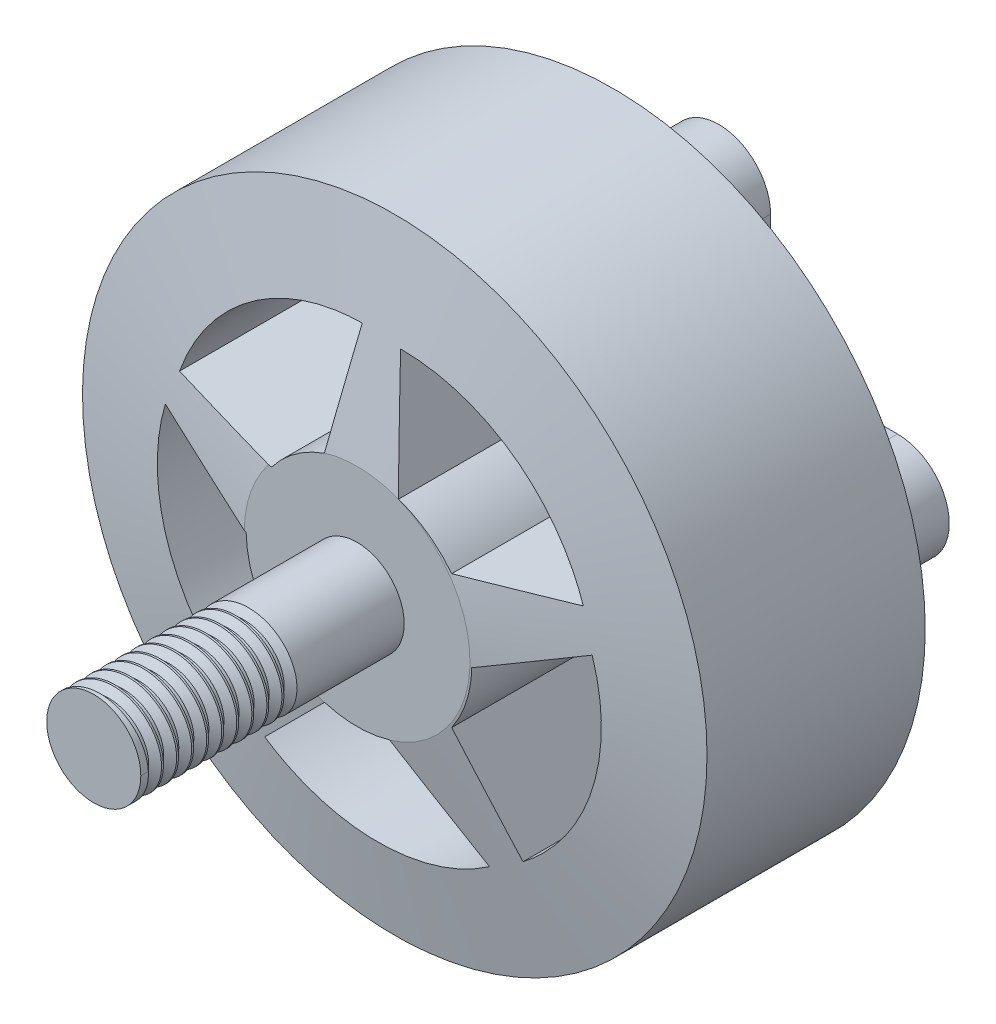
SolidWorks part; units mm, degrees
material "7050-T7651"
ref_plane "Alzado" through (0, 0, 0) normal (0, 0, 1) x (1, 0, 0)
ref_plane "Planta" through (0, 0, 0) normal (0, 1, 0) x (1, 0, 0)
ref_plane "Vista lateral" through (0, 0, 0) normal (1, 0, 0) x (0, 0, -1)
sketch "Croquis1" plane through (0, 0, 0) normal (0, 0, 1) x (1, 0, 0)
  line L0 (0, 0) -> (5.4801, 5.4801) construction
  line L1 (0, 0) -> (-5.4801, 5.4801) construction
  line L2 (-2.75, 9.5) -> (-2.75, 8.5147)
  line L3 (2.75, 9.5) -> (2.75, 8.5147)
  line L4 (9.5, 2.75) -> (8.5147, 2.75)
  line L5 (9.5, -2.75) -> (8.5147, -2.75)
  line L6 (2.75, -9.5) -> (2.75, -8.5147)
  line L7 (-2.75, -9.5) -> (-2.75, -8.5147)
  line L8 (-9.5, -2.75) -> (-8.5147, -2.75)
  line L9 (-9.5, 2.75) -> (-8.5147, 2.75)
  line L10 (12.25, 0) -> (11.25, 0) construction
  circle A0 centre (0, 0) radius 9.5 construction
  circle A1 centre (0, 9.5) radius 1.75
  arc A2 (-3.7756, 6.7681) -> (-5.4801, 5.4801) centre (0, 0) ccw
  arc A3 (2.75, 9.5) -> (-2.75, 9.5) centre (0, 9.5) ccw
  arc A4 (5.4801, 5.4801) -> (3.7756, 6.7681) centre (0, 0) ccw
  arc A5 (2.75, 8.5147) -> (3.7756, 6.7681) centre (4.75, 8.5147) ccw
  arc A6 (-2.75, 8.5147) -> (-3.7756, 6.7681) centre (-4.75, 8.5147) cw
  circle A7 centre (9.5, 0) radius 1.75
  arc A8 (6.7681, 3.7756) -> (5.4801, 5.4801) centre (0, 0) ccw
  arc A9 (9.5, -2.75) -> (9.5, 2.75) centre (9.5, 0) ccw
  arc A10 (5.4801, -5.4801) -> (6.7681, -3.7756) centre (0, 0) ccw
  arc A11 (8.5147, -2.75) -> (6.7681, -3.7756) centre (8.5147, -4.75) ccw
  arc A12 (8.5147, 2.75) -> (6.7681, 3.7756) centre (8.5147, 4.75) cw
  circle A13 centre (0, -9.5) radius 1.75
  arc A14 (3.7756, -6.7681) -> (5.4801, -5.4801) centre (0, 0) ccw
  arc A15 (-2.75, -9.5) -> (2.75, -9.5) centre (0, -9.5) ccw
  arc A16 (-5.4801, -5.4801) -> (-3.7756, -6.7681) centre (0, 0) ccw
  arc A17 (-2.75, -8.5147) -> (-3.7756, -6.7681) centre (-4.75, -8.5147) ccw
  arc A18 (2.75, -8.5147) -> (3.7756, -6.7681) centre (4.75, -8.5147) cw
  circle A19 centre (-9.5, 0) radius 1.75
  arc A20 (-6.7681, -3.7756) -> (-5.4801, -5.4801) centre (0, 0) ccw
  arc A21 (-9.5, 2.75) -> (-9.5, -2.75) centre (-9.5, 0) ccw
  arc A22 (-5.4801, 5.4801) -> (-6.7681, 3.7756) centre (0, 0) ccw
  arc A23 (-8.5147, 2.75) -> (-6.7681, 3.7756) centre (-8.5147, 4.75) ccw
  arc A24 (-8.5147, -2.75) -> (-6.7681, -3.7756) centre (-8.5147, -4.75) cw
  circle A25 centre (0, 0) radius 4
  point P54 (0, 0)
  dimension "D1" = 2
  dimension "D3" = 19
  dimension "D4" = 1
  dimension "D2" = 4
extrude "Saliente-Extruir1" add sketch "Croquis1" along normal blind 2.5 contours L8 A24 A20 A16 A17 L7 A15 L6 A18 A14 A10 A11 L5 A9 L4 A12 A8 A4 A5 L3 A3 L2 A6 A2 A22 A23 L9 A21 A25 A1 A7 A13 A19 region at (0, 11.9035, 0)
sketch "Croquis2" plane through (0, 0, 0) normal (0, 1, 0) x (1, 0, 0)
  line L0 (-0.1267, -2.5) -> (-5.1267, -2.5)
  line L1 (-4.0348, -5.5) -> (-16.7267, -5.5)
  line L2 (-5.1267, -2.5) -> (-4.0348, -5.5)
  line L4 (-16.7267, -5.5) -> (-16.7267, -17.1)
  line L5 (-16.7267, -17.1) -> (-6.1267, -19.1)
  line L6 (-6.1267, -19.1) -> (-2.6267, -19.1)
  line L7 (-2.6267, -19.1) -> (-2.6267, -33.1)
  line L8 (-2.6267, -33.1) -> (-0.1267, -33.1)
  line L9 (-0.1267, -33.1) -> (-0.1267, -2.5)
  line L10 (-6.7681, -2.5) -> (-3.7756, -2.5) construction
  point P8 (0, 0)
  dimension "D1" = 5
  dimension "D2" = 70
  dimension "D3" = 3
  dimension "D4" = 16.6
  dimension "D5" = 2
  dimension "D6" = 30.6
  dimension "D7" = 6
  dimension "D8" = 3.5
  dimension "D9" = 14
  dimension "D10" = 0
revolve "Revolución1" add sketch "Croquis2" angle 360 about L9
thread "Rosca1" pitch 0.8 method cut profile "Perfil de rosca1" start angle 0, offset 0, length 8, pitch 0.8, diameter 5
ref_plane "Plano1" through (-2.6267, 0, 33.1) normal (0, -1, 0) x (-1, 0, 0)
sketch "Perfil de rosca1" plane through (-2.6267, 0, 33.1) normal (0, -1, 0) x (-1, 0, 0)
  line L0 (0, 0) -> (0, 0.8) construction
  line L11 (0, 0) -> (0, 0.7)
  line L12 (0, 0.7) -> (-0.433, 0.45)
  line L13 (-0.433, 0.45) -> (-0.433, 0.25)
  line L15 (-0.433, 0.25) -> (0, 0)
  line L17 (-0.433, 0.35) -> (0, 0.35) construction
  point P2 (0, 0)
  dimension "Pitch" = 0.8
  dimension "Profile_Angle" = 60
  dimension "Profile_Land" = 0.2
  dimension "Profile_Height" = 0.433
sketch "Croquis6" plane through (0, 0, 19.1) normal (0, 0, 1) x (1, 0, 0)
  line L0 (-0.1267, -6) -> (1.8733, -6) construction
  line L1 (-0.1267, -6) -> (-2.1267, -6) construction
  line L2 (-2.1267, -6) -> (-1.8595, -5.7328) construction
  line L3 (1.8733, -6) -> (1.6061, -5.7328) construction
  line L4 (-1.8595, -5.7328) -> (-6.1022, -9.9755)
  line L5 (1.6061, -5.7328) -> (5.8488, -9.9755)
  line L6 (-6.0269, -0.003) -> (-11.3729, 2.7209)
  line L7 (-4.9559, -3.2991) -> (-7.6799, -8.6451)
  line L8 (-5.7455, -1.7336) -> (-5.1275, -3.6357) construction
  line L9 (-5.7455, -1.7336) -> (-6.3635, 0.1685) construction
  line L10 (-6.3635, 0.1685) -> (-6.0269, -0.003) construction
  line L11 (-5.1275, -3.6357) -> (-4.9559, -3.2991) construction
  line L12 (-1.8653, 5.731) -> (-0.9267, 11.6571)
  line L13 (-4.6691, 3.6939) -> (-10.5952, 4.6325)
  line L14 (-3.4242, 4.9286) -> (-5.0423, 3.753) construction
  line L15 (-3.4242, 4.9286) -> (-1.8062, 6.1041) construction
  line L16 (-1.8062, 6.1041) -> (-1.8653, 5.731) construction
  line L17 (-5.0423, 3.753) -> (-4.6691, 3.6939) construction
  line L18 (4.8741, 3.545) -> (10.8002, 4.4836)
  line L19 (2.0703, 5.582) -> (1.1317, 11.5082)
  line L20 (3.6292, 4.7796) -> (2.0112, 5.9552) construction
  line L21 (3.6292, 4.7796) -> (5.2472, 3.6041) construction
  line L22 (5.2472, 3.6041) -> (4.8741, 3.545) construction
  line L23 (2.0112, 5.9552) -> (2.0703, 5.582) construction
  line L24 (4.8776, -3.5401) -> (7.6016, -8.8861)
  line L25 (5.9486, -0.244) -> (11.2946, 2.4799)
  line L26 (5.6672, -1.9746) -> (6.2852, -0.0725) construction
  line L27 (5.6672, -1.9746) -> (5.0492, -3.8767) construction
  line L28 (5.0492, -3.8767) -> (4.8776, -3.5401) construction
  line L29 (6.2852, -0.0725) -> (5.9486, -0.244) construction
  circle A0 centre (-0.1267, 0) radius 6 construction
  arc A1 (-1.8595, -5.7328) -> (1.6061, -5.7328) centre (-0.1267, 0.0243) ccw
  circle A2 centre (-0.1267, 0.0243) radius 13.5502 construction
  arc A3 (-6.1022, -9.9755) -> (5.8488, -9.9755) centre (-0.1267, -1.4082) ccw
  arc A4 (-6.0269, -0.003) -> (-4.9559, -3.2991) centre (-0.0161, 0.128) ccw
  arc A5 (-11.3729, 2.7209) -> (-7.6799, -8.6451) centre (-1.3785, -0.3147) ccw
  arc A6 (-1.8653, 5.731) -> (-4.6691, 3.6939) centre (0.1167, 0.0548) ccw
  arc A7 (-0.9267, 11.6571) -> (-10.5952, 4.6325) centre (-0.7252, 1.2137) ccw
  arc A8 (4.8741, 3.545) -> (2.0703, 5.582) centre (0.0882, -0.0941) ccw
  arc A9 (10.8002, 4.4836) -> (1.1317, 11.5082) centre (0.9302, 1.0648) ccw
  arc A10 (4.8776, -3.5401) -> (5.9486, -0.244) centre (-0.0622, -0.113) ccw
  arc A11 (7.6016, -8.8861) -> (11.2946, 2.4799) centre (1.3002, -0.5557) ccw
  point P50 (0, 0)
  dimension "D1" = 2
  dimension "D2" = 5
extrude "Cortar-Extruir1" cut sketch "Croquis6" against normal up to surface (13.6 mm away) up to face at (16.4733, 0, 5.5)
